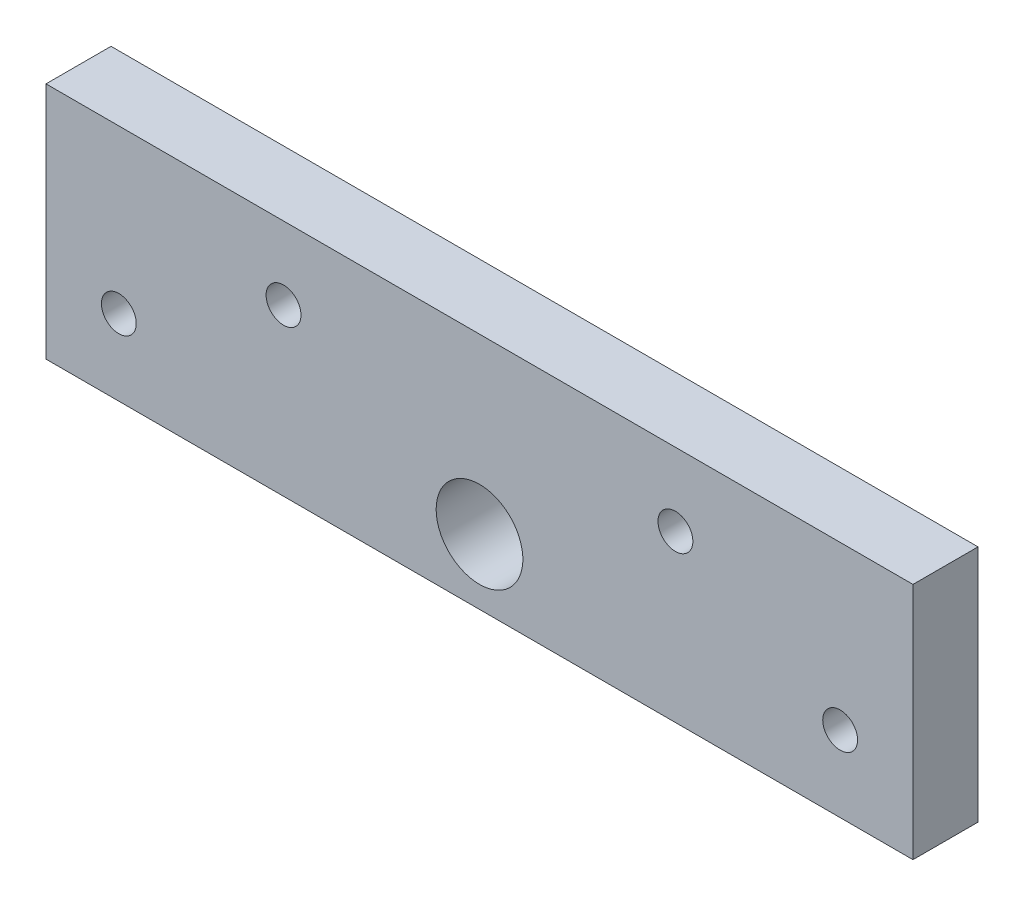
SolidWorks part; units mm, degrees
material "6061-T6 (SS)"
ref_plane "Front Plane" through (0, 0, 0) normal (0, 0, 1) x (1, 0, 0)
ref_plane "Top Plane" through (0, 0, 0) normal (0, 1, 0) x (1, 0, 0)
ref_plane "Right Plane" through (0, 0, 0) normal (1, 0, 0) x (0, 0, -1)
sketch "Sketch8" plane through (0, 0, 0) normal (0, 0, 1) x (1, 0, 0)
  line B0 (-63.5, -15.875) -> (63.5, -15.875)
  line B1 (63.5, -15.875) -> (63.5, 0)
  line B2 (36.5092, 0) -> (47.625, 15.875)
  line B3 (47.625, 15.875) -> (16.0563, 15.875)
  line B4 (-39.8731, 15.875) -> (-28.7573, 0)
  line B5 (-28.7573, 0) -> (-63.5, 0)
  line B6 (-36.5092, 0) -> (-47.625, 15.875)
  line B7 (-47.625, 15.875) -> (-39.8731, 15.875)
  line B8 (-16.0563, 15.875) -> (-16.0563, -3.175)
  line B9 (-16.0563, -3.175) -> (16.0563, -3.175)
  line B10 (16.0563, -3.175) -> (16.0563, 15.875)
  line B11 (-16.0563, 15.875) -> (-39.8731, 15.875)
  line B12 (-63.5, 0) -> (-63.5, 31.75)
  line B13 (-63.5, 31.75) -> (63.5, 31.75)
  line B14 (-16.0563, 15.875) -> (16.0563, 15.875)
  line B15 (0, 31.75) -> (0, -15.875) construction
  line B16 (-36.5092, 0) -> (36.5092, 0) construction
  line B17 (-28.702, 21.082) -> (28.702, 21.082) construction
  line B18 (-25.4, -8.001) -> (25.4, -8.001) construction
  line B19 (-25.4, -8.001) -> (-25.4, 7.9375) construction
  line B20 (-52.832, 7.9375) -> (52.832, 7.9375) construction
  circle B21 centre (0, 6.35) radius 18.669 construction
  line B22 (39.8731, 15.875) -> (28.7573, 0)
sketch_block_instance "dovetail pair-1"
sketch_block "Block1" parameters "D8"=37.338, "D1"=55, "D2"=127, "D3"=6.35, "D4"=15.875, "D5"=31.75, "D6"=95.25, "D7"=19.05, "D9"=55, "D10"=31.75, "D11"=50.8, "D12"=23.876, "D13"=7.874, "D14"=10.668, "D15"=34.798, "D16"=21.082, "D17"=7.9375
sketch "Sketch1" plane through (0, 0, 0) normal (0, 0, 1) x (1, 0, 0)
  line L0 (63.5, -15.875) -> (63.5, 0) construction
  line L1 (-63.5, 31.75) -> (63.5, 31.75)
  line L2 (-63.5, 31.75) -> (-63.5, -3.175)
  line L3 (-63.5, -3.175) -> (63.5, -3.175)
  line L4 (63.5, 31.75) -> (63.5, -3.175)
  line L5 (-16.0563, -3.175) -> (16.0563, -3.175) construction
  circle A0 centre (0, 6.35) radius 6.35
  dimension "D1" = 12.7
extrude "Boss-Extrude1" add sketch "Sketch1" along normal blind 9.525
hole_wizard "CBORE for #10 Socket Head Cap Screw1" positions "Sketch6" profile "Sketch7" counterbore size "#10" standard "ANSI Inch" end condition up to next
sketch "Sketch6" plane through (248.3324, -44.45, 0) normal (0, 0, -1) x (-1, 0, 0)
  point P26 (219.6304, 65.532)
  point P28 (195.5004, 52.3875)
  point P30 (277.0344, 65.532)
  point P32 (301.1644, 52.3875)
sketch "Sketch7" plane through (28.702, 21.082, 0) normal (1, 0, 0) x (0, 1, 0)
  line L0 (0, 0) -> (0, 9.525)
  line L1 (0, 9.525) -> (2.5527, 9.525)
  line L3 (2.5527, 9.525) -> (2.5527, 4.826)
  line L4 (4.7625, 4.826) -> (2.5527, 4.826)
  line L5 (4.7625, 4.826) -> (4.7625, 0.635)
  line L6 (4.7625, 0.635) -> (5.3975, 0)
  line L7 (5.3975, 0) -> (0, 0)
  line L8 (-4.7625, 0.635) -> (-5.3975, 0) construction
  line L11 (0, -6.35) -> (0, 107.95) construction
  dimension "Thru Hole Dia." = 5.1054
  dimension "Thru Hole Depth" = 9.525
  dimension "C'Bore Dia." = 9.525
  dimension "C'Bore Depth" = 4.826
  dimension "Near C'Sink Dia." = 10.795
  dimension "Near C'Sink Angle" = 90
equation "\"dovetail-angle\" = 55"
equation "\"dovetail-stock-width\" = 5"
equation "\"dovetail-stock-height\" = 1.25"
equation "\"dovetail-depth\" = 0.5 * \"dovetail-stock-height\""
equation "\"dovetail-throat-width\" = \"dovetail-stock-width\" - (2 * \"dovetail-depth\")"
equation "\"delta-x\" = 6"
equation "\"delta-y\" = 3"
equation "\"gib-thickness\" = 0.25"
equation "\"x-slide-length\" = \"dovetail-stock-width\" + \"delta-x\""
equation "\"y-slide-length\" = \"dovetail-stock-width\" + \"delta-y\""
equation "\"dog-point-diam\" = .149"
equation "\"dog-point-length\" = .067"
equation "\"dovetail-double-height\" = 2 * \"dovetail-depth\" + 0.5"
equation "\"acme-major-diam\" = .5"
equation "\"acme-pitch-diam\" = 0.45"
equation "\"acme-minor-diam\" = 0.4"
equation "\"x-screw-length\" = \"x-slide-length\" + \"screw-add-length\""
equation "\"y-screw-length\" = \"y-slide-length\" + \"screw-add-length\""
equation "\"acme-nut-od\" = 1.47"
equation "\"acme-nut-length\" = 1"
equation "\"acme-nut-trim-height\" = .75"
equation "\"D1@Sketch1\"=\"screw-bearing-od\""
equation "\"screw-bearing-od\" = 0.5"
equation "\"screw-bearing-length\" = .375"
equation "\"end-plate-thickness\" = \"screw-bearing-length\""
equation "\"D1@Boss-Extrude1\"=\"end-plate-thickness\""
equation "\"screw-bearing-id\" = .375"
equation "\"screw-add-length\" = 2 * \"end-plate-thickness\" + 1 + 0.5"
equation "\"acme-nut-mount-hole-space-horz\" = 0.95"
equation "\"acme-nut-mount-hole-space-vert\" = 0.5 * \"acme-nut-length\""
